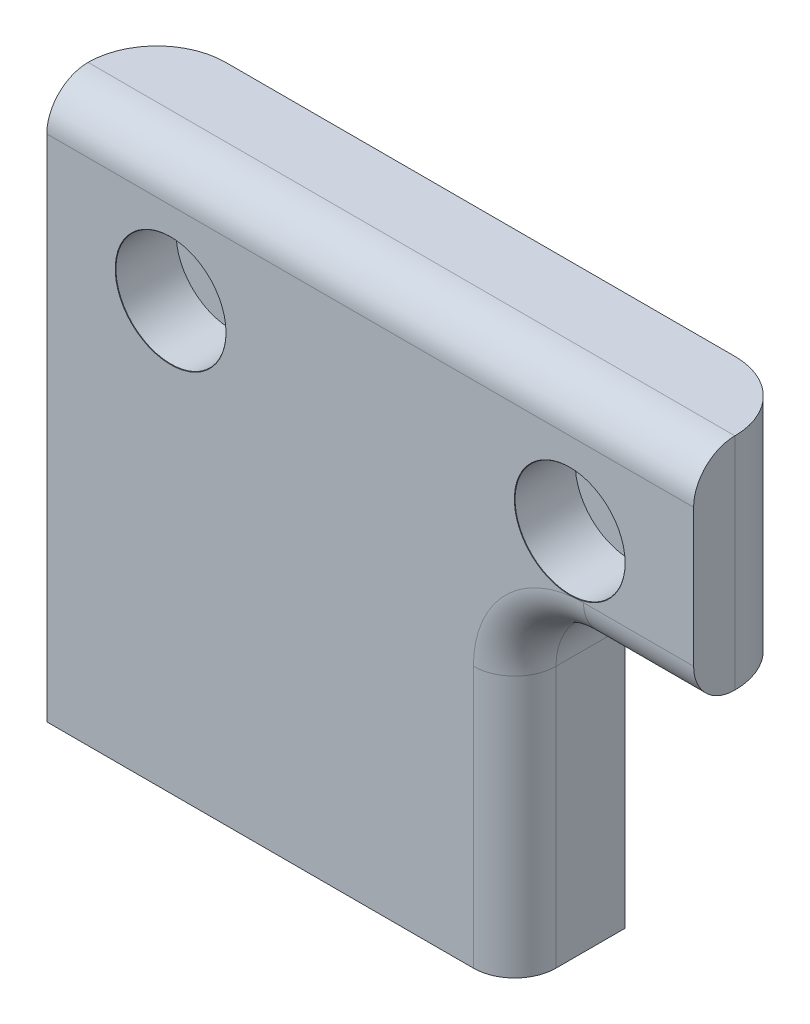
SolidWorks part; units mm, degrees
material "K110"
ref_plane "Front Plane" through (0, 0, 0) normal (0, 0, 1) x (1, 0, 0)
ref_plane "Top Plane" through (0, 0, 0) normal (0, 1, 0) x (1, 0, 0)
ref_plane "Right Plane" through (0, 0, 0) normal (1, 0, 0) x (0, 0, -1)
sketch "Sketch1" plane through (0, 0, 0) normal (0, 1, 0) x (1, 0, 0)
  line L1 (-23.5, -4) -> (23.5, -4)
  line L2 (-23.5, -4) -> (-23.5, 4)
  line L3 (-23.5, 4) -> (23.5, 4)
  line L4 (23.5, -4) -> (23.5, 4)
  line L5 (-23.5, -4) -> (23.5, 4) construction
  line L6 (-23.5, 4) -> (23.5, -4) construction
  point P0 (0, 0)
  dimension "D1" = 8
  dimension "D2" = 47
extrude "Boss-Extrude1" add sketch "Sketch1" against normal blind 40
fillet "Fillet1" radius 3 1 edges at (0, 0, 4)
fillet "Fillet2" radius 5 2 edges at (-23.5, -20, -4) (23.5, -20, -4)
hole_wizard "CBORE for M4 Hex Socket Head Cap Screw1" positions "Sketch6" profile "Sketch3" counterbore size "M4" standard "ISO" end condition through all
sketch "Sketch6" plane through (0, 0, 4) normal (0, 0, 1) x (1, 0, 0)
  line L1 (23.5, -3) -> (-23.5, -3) construction
  line L2 (-23.5, -40) -> (-23.5, -3) construction
  line L3 (23.5, -40) -> (23.5, -3) construction
  point P0 (-14.5, -9)
  point P2 (14.5, -9)
  dimension "D1" = 6
  dimension "D2" = 9
  dimension "D3" = 9
sketch "Sketch3" plane through (-14.5, -9, 4) normal (1, 0, 0) x (0, -1, 0)
  line L0 (0, 0) -> (0, 8)
  line L1 (0, 8) -> (2.15, 8)
  line L3 (2.15, 8) -> (2.15, 4.4)
  line L4 (4, 4.4) -> (2.15, 4.4)
  line L5 (4, 4.4) -> (4, 0.025)
  line L6 (4, 0.025) -> (4.025, 0)
  line L7 (4.025, 0) -> (0, 0)
  line L8 (-4, 0.025) -> (-4.025, 0) construction
  line L11 (0, -6.35) -> (0, 107.95) construction
  dimension "Thru Hole Dia." = 4.3
  dimension "Thru Hole Depth" = 8
  dimension "C'Bore Dia." = 8
  dimension "C'Bore Depth" = 4.4
  dimension "Near C'Sink Dia." = 8.05
  dimension "Near C'Sink Angle" = 90
sketch "Sketch5" plane through (0, 0, 4) normal (0, 0, 1) x (1, 0, 0)
  line L0 (23.5, -40) -> (23.5, -3) construction
  line L1 (23.5, -40) -> (10.5, -40)
  line L2 (23.5, -40) -> (23.5, -16.0022)
  line L3 (23.5, -16.0022) -> (10.5, -16.0022)
  line L4 (10.5, -40) -> (10.5, -16.0022)
  line L5 (23.5, -16.0022) -> (29.5, -16.0022) construction
  dimension "D2" = 13
extrude "Cut-Extrude1" cut sketch "Sketch5" against normal up to next
fillet "Fillet3" radius 5 1 edges at (10.5, -16.0022, 0)
fillet "Fillet4" radius 3 3 edges at (19.5, -16.0022, 4) (11.9645, -17.4667, 4) (10.5, -30.5011, 4)
